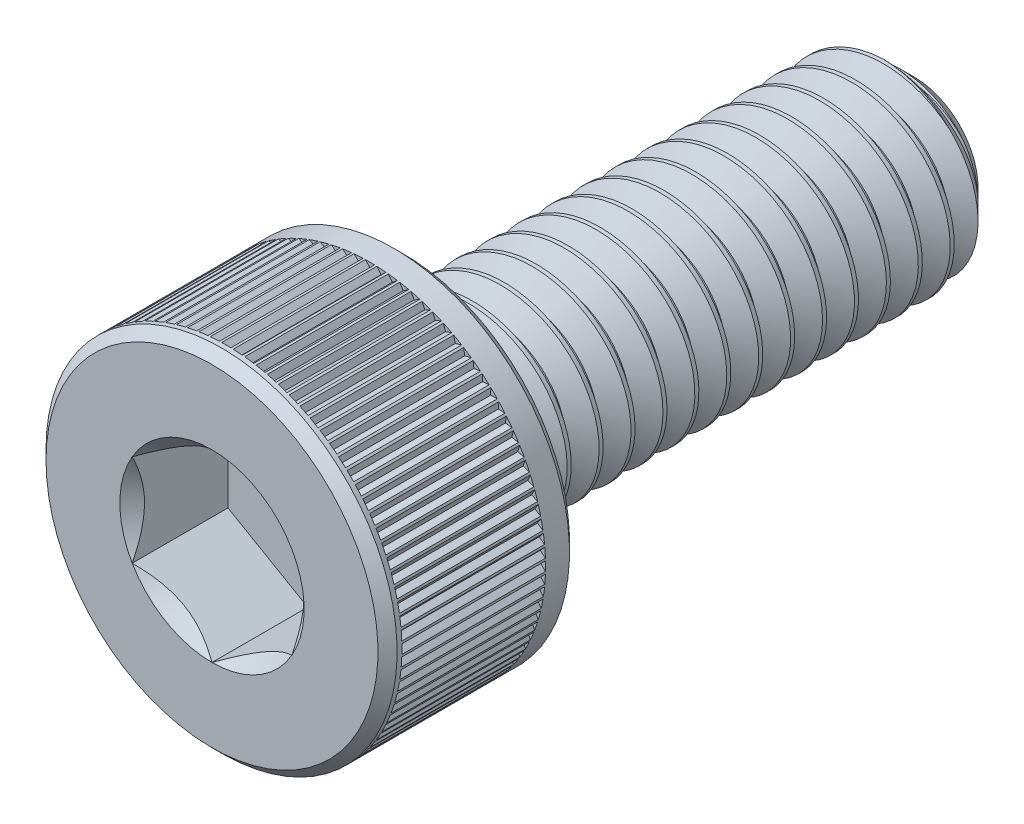
SolidWorks part; units mm, degrees
ref_plane "Front Plane" through (0, 0, 0) normal (0, 0, 1) x (1, 0, 0)
ref_plane "Top Plane" through (0, 0, 0) normal (0, 1, 0) x (1, 0, 0)
ref_plane "Right Plane" through (0, 0, 0) normal (1, 0, 0) x (0, 0, -1)
sketch "Sketch1" plane through (0, 0, 0) normal (1, 0, 0) x (0, 0, -1)
  line L0 (-5.5, 0) -> (5.5, 0) construction
  line L1 (5.5, 0) -> (5.5, 1) construction
  line L2 (5.5, 1) -> (5, 1.5) construction
  line L3 (5, 1.5) -> (-2.5, 1.5) construction
  line L5 (-2.5, 1.5) -> (-2.5, 2.75) construction
  line L6 (-2.5, 2.75) -> (-5.5, 2.75) construction
  line L7 (-5.5, 2.75) -> (-5.5, 0) construction
  line L8 (5.5, 1) -> (5.5, 1.5) construction
  line L9 (5.4688, 1.5541) -> (5.7188, 1.1211) construction
  line L10 (5.7188, 1.1211) -> (5.9688, 1.5541) construction
  line L11 (5.9688, 1.5541) -> (5.4688, 1.5541) construction
  line L12 (5.7188, 1.5541) -> (5.7188, 1.5) construction
  line L13 (5.7188, 1.1211) -> (5.7188, 1.1752) construction
  line L14 (5.6875, 1.1752) -> (5.75, 1.1752) construction
  line L15 (5.5, 1.5) -> (5.9375, 1.5) construction
  line L16 (5.4844, 1.5271) -> (5.9531, 1.5271) construction
  line L17 (5.5, 0) -> (5.5, -1.5) construction
  line L18 (-2.65, 2.75) -> (-2.5, 2.6) construction
  line L19 (-5.35, 2.75) -> (-5.5, 2.6) construction
  point P0 (-5.5, 1.25)
  point P3 (3.75, 1.5)
  point P4 (0, 0)
  point P22 (5.7188, 1.1752)
  point P24 (-2.5, 1.5)
  point P25 (5.7188, 1.5)
  point P28 (5.7188, 1.5271)
  point P29 (3.75, -1.5)
  point P31 (-4, 2.75)
  point P37 (-3.025, 2.75)
  point P38 (-5.275, 2.75)
  point P41 (-4, 0)
  dimension "head height" = 3
  dimension "D1" = 45
  dimension "Head Diameter" = 5.5
  dimension "Thread Size" = 3
  dimension "drive size" = 2.5
  dimension "Thread Pitch" = 0.5
  dimension "D2" = 0.0625
  dimension "D3" = 0.5
  dimension "D4" = 1.75
  dimension "D7" = 0.15
  dimension "D8" = 0.15
  dimension "D9" = 0.15
  dimension "D10" = 0.075
  dimension "D11" = 0.375
  dimension "length" = 8
  dimension "Drive Depth" = 1.5
sketch "Sketch2" plane through (0, 0, 0) normal (1, 0, 0) x (0, 0, -1)
  line L1 (-5.35, 2.75) -> (-2.65, 2.75)
  line L4 (5, 1.5) -> (5.5, 1)
  line L5 (5.5, 1) -> (5.5, 0)
  line L6 (-2.65, 2.75) -> (-2.5, 2.6) construction
  line L7 (5.5, 0) -> (-5.5, 0)
  line L8 (-5.35, 2.75) -> (-5.5, 2.6) construction
  line L9 (-2.65, 2.75) -> (-2.5, 2.6)
  line L10 (-5.35, 2.75) -> (-5.5, 2.6)
  line L11 (-5.5, 2.6) -> (-5.5, 0)
  line L12 (-2.5, 2.6) -> (-2.5, 1.5)
  line L13 (-2.5, 1.5) -> (5, 1.5)
revolve "Revolve1" add sketch "Sketch2" angle 360 about L7
sketch "Sketch3" plane through (0, 0, 5.5) normal (0, 0, 1) x (1, 0, 0)
  line L1 (0, 1.4434) -> (-1.25, 0.7217)
  line L2 (-1.25, 0.7217) -> (-1.25, -0.7217)
  line L3 (-1.25, -0.7217) -> (0, -1.4434)
  line L4 (0, -1.4434) -> (1.25, -0.7217)
  line L5 (1.25, -0.7217) -> (1.25, 0.7217)
  line L6 (1.25, 0.7217) -> (0, 1.4434)
  circle A0 centre (0, 0) radius 1.25 construction
  dimension "D1" = 2.5
extrude "Cut-Extrude1" cut sketch "Sketch3" against normal up to vertex (1.5 mm away) up to point (0, 0, 4)
sketch "Sketch4" plane through (0, 0, 5.5) normal (0, 0, 1) x (1, 0, 0)
  circle A0 centre (0, 0) radius 1.4434
extrude "Cut-Extrude2" cut sketch "Sketch4" against normal blind 0.5 draft 45
ref_plane "Plane1" through (0, 0, 2.5) normal (0, 0, 1) x (1, 0, 0)
split "Split1" bodies to split 106 resulting bodies 108 115 split by face at (-2.6, 0, 2.5)
sketch "Sketch6" plane through (0, 0, -5.5) normal (0, 0, -1) x (-1, 0, 0)
  circle A0 centre (0, 0) radius 1.5
curve "Helix/Spiral1" pitch 0.5 height 8.5 radius 1.5 centre (0, 0, -5.5) axis (0, 0, 1) start towards (0, 1, 0)
sketch "Sketch7" plane through (0, 0, 0) normal (1, 0, 0) x (0, 0, -1)
  line L0 (5.4844, 1.5271) -> (5.9531, 1.5271)
  line L1 (5.9531, 1.5271) -> (5.75, 1.1752)
  line L2 (5.75, 1.1752) -> (5.6875, 1.1752)
  line L3 (5.6875, 1.1752) -> (5.4844, 1.5271)
sweep "Cut-Sweep1" cut profiles "Sketch7" path "Helix/Spiral1" align with end faces yes
sketch "Sketch8" plane through (0, 0, 2.5) normal (0, 0, -1) x (-1, 0, 0)
  circle A0 centre (0, 0) radius 1.5
extrude "Boss-Extrude1" add sketch "Sketch8" along normal through all draft 45
ref_plane "Plane2" through (0, 0, 4) normal (0, 0, 1) x (1, 0, 0)
sketch "Sketch9" plane through (0, 0, 4) normal (0, 0, 1) x (1, 0, 0)
  line L0 (0, 2.6744) -> (0.072, 2.7491)
  line L1 (0, 2.6744) -> (-0.072, 2.7491)
  line L2 (0, 2.75) -> (0, 0) construction
  line L3 (-0.072, 2.7491) -> (0, 0) construction
  line L4 (0, 0) -> (0.072, 2.7491) construction
  arc A0 (0.072, 2.7491) -> (-0.072, 2.7491) centre (0, 0) ccw
  circle A1 centre (0, 0) radius 2.6744 construction
  dimension "D1" = 5.5
  dimension "D2" = 5.3487
  dimension "D3" = 3
extrude "Cut-Extrude4" cut sketch "Sketch9" against normal up to vertex (0.975 mm away) and the other way up to vertex (1.275 mm away) up to point (0, 2.75, 3.025) other way up to point (0, 2.75, 5.275)
pattern_circular "CirPattern2" count 96 over 360 about axis through (0, 0, 5.5) along (0, 0, -1) of "Cut-Extrude4"
equation "\"D2@Sketch1\" = \"Thread Pitch@Sketch1\" / 8"
equation "\"D3@Sketch1\" = \"Thread Pitch@Sketch1\""
equation "\"D3@Helix/Spiral1\" = \"length@Sketch1\" + \"Thread Pitch@Sketch1\""
equation "\"D4@Helix/Spiral1\" = \"Thread Pitch@Sketch1\""
equation "\"D4@Sketch1\" = \"Thread Pitch@Sketch1\" * 3.5"
equation "\"D7@Sketch1\"=\"head height@Sketch1\"*.05"
equation "\"D8@Sketch1\"=\"D7@Sketch1\""
equation "\"D9@Sketch1\"=\"D7@Sketch1\""
equation "\"D10@Sketch1\"=\"D7@Sketch1\"/2"
equation "\"D11@Sketch1\"=\"D10@Sketch1\"*5"
equation "\"D1@CirPattern2\"=( 360 / \"D3@Sketch9\" )*0.8"
equation "\"D1@Sketch3\" = \"drive size@Sketch1\""
equation "\"D2@Sketch9\"=\"Head Diameter@Sketch1\" * 0.9725"
